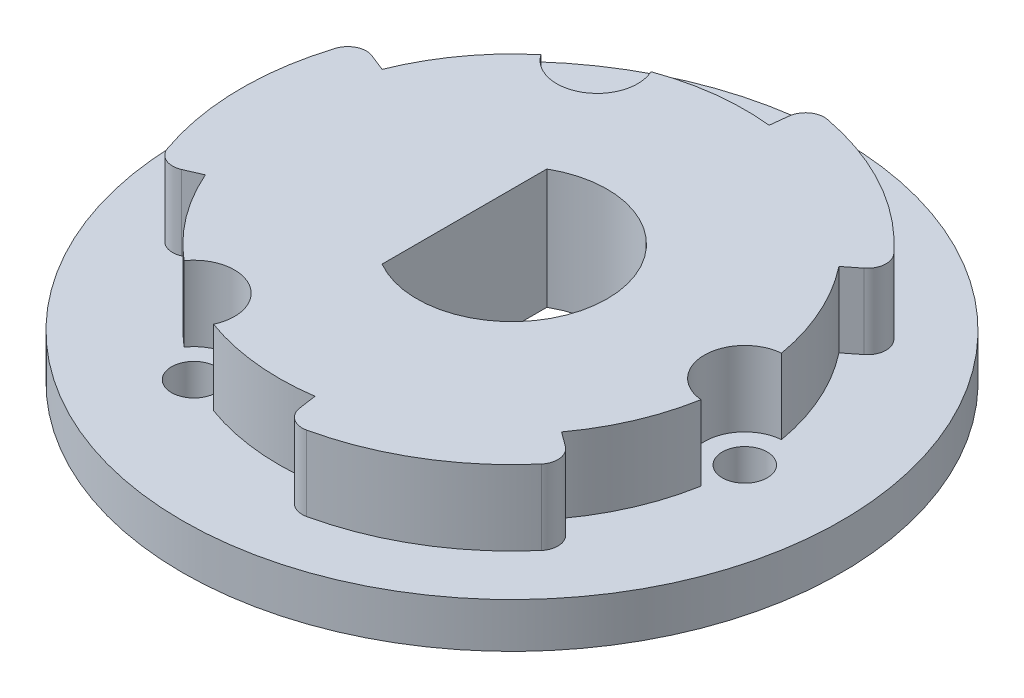
SolidWorks part; units mm, degrees
ref_plane "Front Plane" through (0, 0, 0) normal (0, 0, 1) x (1, 0, 0)
ref_plane "Top Plane" through (0, 0, 0) normal (0, 1, 0) x (1, 0, 0)
ref_plane "Right Plane" through (0, 0, 0) normal (1, 0, 0) x (0, 0, -1)
sketch "Sketch1" plane through (0, 0, 0) normal (0, 1, 0) x (1, 0, 0)
  line L0 (0, 0) -> (1.716, 15.445) construction
  line L1 (0, 0) -> (12.2062, 9.6177) construction
  line L2 (12.2062, 9.6177) -> (1.716, 15.445) construction
  line L3 (12.2062, 9.6177) -> (15.4676, 1.4983) construction
  line L4 (1.716, 15.445) -> (1.8489, 16.641)
  line L5 (12.2062, 9.6177) -> (13.1514, 10.3625)
  line L6 (0, 0) -> (13.5415, 7.6235) construction
  line L7 (13.5415, 7.6235) -> (13.5415, -7.6235) construction
  line L8 (13.5415, -7.6235) -> (0, 0) construction
  line L9 (13.5415, 7.6235) -> (14.5902, 8.2139)
  line L10 (13.5415, -7.6235) -> (14.5902, -8.2139)
  line L11 (0, 0) -> (19.54, 0) construction
  circle A0 centre (0, 0) radius 15.54
  circle A1 centre (0, 0) radius 19.54
  circle A2 centre (0, 0) radius 18.04
  circle A3 centre (0, 0) radius 15.54
  circle A4 centre (15.54, 0) radius 1.5
  circle A5 centre (15.54, 0) radius 2.7
  circle A6 centre (3.0913, 16.503) radius 1.25
  circle A7 centre (12.3778, 11.3443) radius 1.25
  circle A8 centre (15.2034, 7.1246) radius 1.25
  circle A9 centre (15.2034, -7.1246) radius 1.25
  point P24 (13.5415, 0)
  dimension "D1" = 31.08
  dimension "D2" = 4
  dimension "D3" = 1.5
  dimension "D4" = 3
  dimension "D5" = 1.2
  dimension "D6" = 12
  dimension "D8" = 2.4
  dimension "D7" = 8.75
extrude "Boss-Extrude1" add sketch "Sketch1" along normal blind 7.9 contours A1 | A0
extrude "Boss-Extrude2" add sketch "Sketch1<3>" along normal up to surface (7.9 mm away) contours A5 up to face at (0, 7.9, 19.54)
sketch "Sketch1<3>" plane through (0, 0, 0) normal (0, 1, 0) x (1, 0, 0) same geometry as "Sketch1"
extrude "Cut-Extrude1" cut sketch "Sketch1<4>" against normal through all both and the other way through all contours A4
sketch "Sketch1<4>" plane through (0, 0, 0) normal (0, 1, 0) x (1, 0, 0) same geometry as "Sketch1"
extrude "Cut-Extrude2" cut sketch "Sketch1<5>" against normal through all both and the other way through all contours A6 L4 A3 | A6 | A7 A2 A6 A3 | A7 | A7 A0 L5 region at (2.0013, 0, -15.6802) region at (3.0913, 0, -16.503) region at (8.0751, 0, -14.5367) region at (12.2552, 0, -9.9842) region at (12.3778, 0, -11.3443)
sketch "Sketch1<5>" plane through (0, 0, 0) normal (0, 1, 0) x (1, 0, 0) same geometry as "Sketch1"
extrude "Cut-Extrude5" cut sketch "Sketch1<6>" along normal blind 3 contours A8 L9 A0 | A8 | A8 A3 A5 A2 | A2 A5 A0 A4 A3 | A9 A2 A5 A3 | A9 | A9 A0 L10 | A5 | A0 region at (13.8991, 0, 7.5292) region at (15.2034, 0, 7.1246) region at (16.3146, 0, 4.2837) region at (15.458, 0, 2.1038) region at (16.3146, 0, -4.2837) region at (15.2034, 0, -7.1246) region at (13.8991, 0, -7.5292)
sketch "Sketch1<6>" plane through (0, 0, 0) normal (0, 1, 0) x (1, 0, 0) same geometry as "Sketch1"
pattern_circular "CirPattern1" count 3 over 360 about axis through (0, 7.9, 0) along (0, -1, 0) of "Boss-Extrude2", "Cut-Extrude1", "Cut-Extrude2", "Cut-Extrude5"
sketch "Sketch2" plane through (0, 0, 0) normal (0, 1, 0) x (1, 0, 0)
  circle A0 centre (0, 0) radius 26
  circle A1 centre (0, 0) radius 19.54
  circle A2 centre (0, 0) radius 22
  circle A3 centre (0, 0) radius 19.54 construction
  dimension "D1" = 52
  dimension "D2" = 4
extrude "Boss-Extrude3" add sketch "Sketch2" along normal up to surface (7.9 mm away) contours A0 | A1 up to face at (-9.069, 7.9, 12.708)
extrude "Cut-Extrude4" cut sketch "Sketch2<3>" against normal blind 3.14 from surface contours A2 | A1 starting at face at (-9.069, 7.9, 12.708)
sketch "Sketch2<3>" plane through (0, 0, 0) normal (0, 1, 0) x (1, 0, 0) same geometry as "Sketch2"
extrude "Cut-Extrude6" cut sketch "Sketch2<4>" along normal blind 3 contours A2
sketch "Sketch2<4>" plane through (0, 0, 0) normal (0, 1, 0) x (1, 0, 0) same geometry as "Sketch2"
ref_plane "Plane1" through (0, -20, 0) normal (0, -1, 0) x (-1, 0, 0)
sketch "Sketch4" plane through (0, -20, 0) normal (0, -1, 0) x (-1, 0, 0)
  line L0 (14.4323, 5.762) -> (15.5499, 6.2082)
  line L1 (14.2338, -6.2363) -> (15.336, -6.7193)
  line L2 (-12.5177, -9.2086) -> (-13.4871, -9.9217)
  line L3 (-2.2261, -15.3797) -> (-2.3985, -16.5707)
  line L4 (-1.716, 15.445) -> (-1.8489, 16.641)
  line L5 (-12.2062, 9.6177) -> (-13.1514, 10.3625)
  arc A0 (5.3233, 14.5998) -> (9.9822, 11.91) centre (7.77, 13.458) ccw
  arc A1 (9.9822, 11.91) -> (14.4323, 5.762) centre (0, 0) cw
  arc A2 (14.2338, -6.2363) -> (9.9822, -11.91) centre (0, 0) cw
  arc A3 (9.9822, -11.91) -> (5.3233, -14.5998) centre (7.77, -13.458) ccw
  arc A4 (-2.2261, -15.3797) -> (5.3233, -14.5998) centre (0, 0) ccw
  arc A5 (-15.3054, -2.6898) -> (-12.5177, -9.2086) centre (0, 0) ccw
  arc A6 (-15.3054, 2.6898) -> (-15.3054, -2.6898) centre (-15.54, 0) cw
  arc A7 (-15.3054, 2.6898) -> (-12.2062, 9.6177) centre (0, 0) cw
  arc A8 (-1.716, 15.445) -> (5.3233, 14.5998) centre (0, 0) cw
  arc A9 (15.5499, 6.2082) -> (17.2056, 5.4231) centre (16.0134, 5.0473) cw
  arc A10 (15.336, -6.7193) -> (17.0167, -5.9894) centre (15.8376, -5.5744) ccw
  arc A11 (-13.4871, -9.9217) -> (-13.6953, -11.7422) centre (-12.7463, -10.9286) ccw
  arc A12 (-2.3985, -16.5707) -> (-3.9063, -17.612) centre (-3.6356, -16.3917) cw
  arc A13 (-1.8489, 16.641) -> (-3.3214, 17.7316) centre (-3.0913, 16.503) ccw
  arc A14 (-13.1514, 10.3625) -> (-13.2993, 12.1889) centre (-12.3778, 11.3443) cw
  arc A15 (17.2056, 5.4231) -> (17.0167, -5.9894) centre (0, 0) cw
  arc A16 (-3.9063, -17.612) -> (-13.6953, -11.7422) centre (0, 0) cw
  arc A17 (-13.2993, 12.1889) -> (-3.3214, 17.7316) centre (0, 0) cw
  point P62 (0, 0)
  point P63 (0, 0)
  dimension "D1" = 3
  dimension "D2" = 3
extrude "Boss-Extrude5" add sketch "Sketch4" along normal blind 5 separate body
sketch "Sketch5" plane through (0, -25, 0) normal (0, -1, 0) x (1, 0, 0)
  circle A0 centre (0, 0) radius 22
extrude "Boss-Extrude6" add sketch "Sketch5" along normal blind 3
sketch "Sketch6" plane through (0, -25, 0) normal (0, 1, 0) x (1, 0, 0)
  circle A0 centre (-7.77, 13.458) radius 1.5
  circle A1 centre (15.54, 0) radius 1.5
  circle A2 centre (-7.77, -13.458) radius 1.5
extrude "Cut-Extrude7" cut sketch "Sketch6" against normal blind 3
delete or keep bodies "Body-Delete/Keep 1" bodies 109
sketch "Sketch7" plane through (0, -28, 0) normal (0, -1, 0) x (1, 0, 0)
  line L0 (-3.175, 5.4993) -> (-3.175, -5.4993)
  circle A0 centre (0, 0) radius 6.35
  dimension "D1" = 12.7
  dimension "D2" = 3.175
extrude "Cut-Extrude8" cut sketch "Sketch7" against normal blind 15 contours L0 A0 region at (1.0879, -28, 0)
